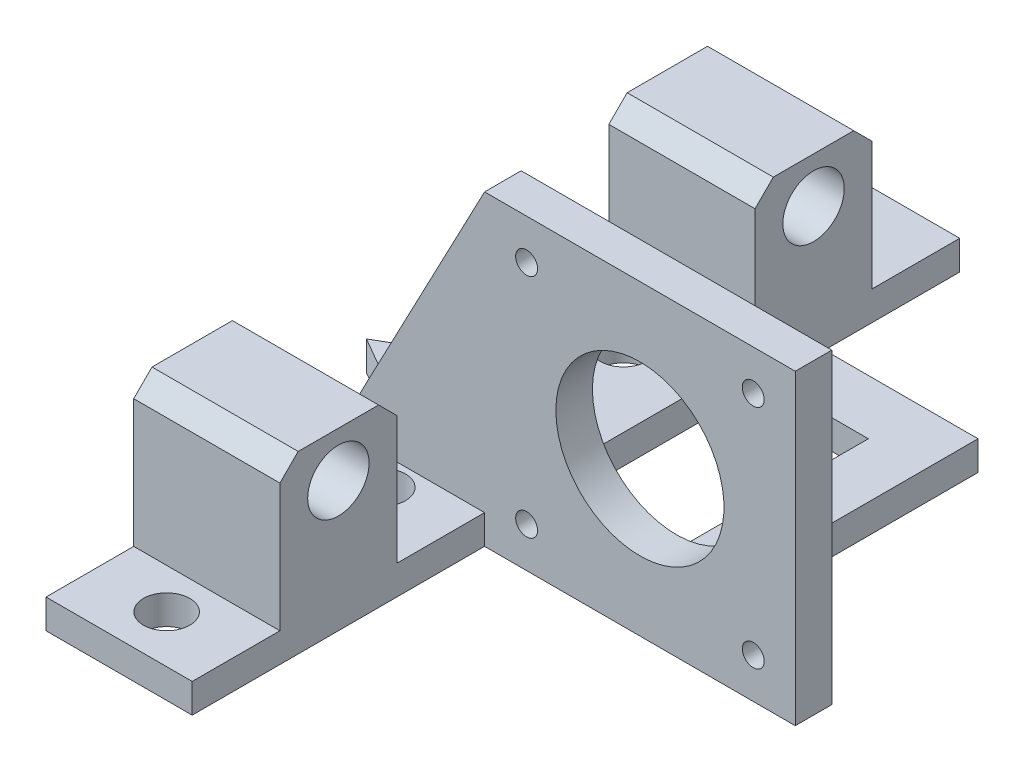
SolidWorks part; units mm, degrees
ref_plane "Front Plane" through (0, 0, 0) normal (0, 0, 1) x (1, 0, 0)
ref_plane "Top Plane" through (0, 0, 0) normal (0, 1, 0) x (1, 0, 0)
ref_plane "Right Plane" through (0, 0, 0) normal (1, 0, 0) x (0, 0, -1)
sketch "Sketch1" plane through (0, 0, 0) normal (0, 1, 0) x (1, 0, 0)
  line L1 (0, 0) -> (20, 0)
  line L2 (0, 0) -> (0, 105)
  line L3 (0, 105) -> (20, 105)
  line L4 (20, 0) -> (20, 105)
  dimension "D1" = 105
  dimension "D2" = 20
extrude "Boss-Extrude1" add sketch "Sketch1" along normal blind 4
sketch "Sketch2" plane through (0, 0, 0) normal (-1, 0, 0) x (0, 0, 1)
  line L0 (-105, 0) -> (0, 0) construction
  line L5 (-12, 21.5) -> (-14.5, 24)
  line L6 (-93, 0) -> (-77, 0)
  line L7 (-93, 0) -> (-93, 24)
  line L8 (-93, 24) -> (-77, 24)
  line L9 (-77, 0) -> (-77, 24)
  line L10 (-105, 0) -> (-93, 0) construction
  line L11 (-79.5, 24) -> (-77, 21.5)
  line L12 (-93, 21.5) -> (-90.5, 24)
  line L13 (-52.5, 0) -> (-52.5, 4) construction
  line L14 (-25.5, 24) -> (-28, 21.5)
  line L15 (-105, 4) -> (0, 4) construction
  line L16 (-28, 0) -> (-28, 24)
  line L17 (-12, 24) -> (-28, 24)
  line L18 (-12, 0) -> (-12, 24)
  line L19 (-12, 0) -> (-28, 0)
  circle A0 centre (-85, 17.8) radius 4.2
  circle A1 centre (-20, 17.8) radius 4.2
  point P10 (-85, 24)
  point P25 (-52.5, 4)
  point P30 (-20, 24)
  line M15 (0, 4) -> (-105, 4)
  dimension "D4" = 8.4
  dimension "D2" = 16
  dimension "D3" = 24
  dimension "D6" = 2.5
  dimension "D7" = 2.5
  dimension "D8" = 2.5
  dimension "D9" = 2.5
  dimension "D1" = 65
  dimension "D5" = 6.2
extrude "Boss-Extrude2" add sketch "Sketch2" against normal up to surface (20 mm away) contours L18 L5 L17 L14 L16 A1 M15 | L12 L7 L9 L11 L8 A0 M15 region at (0, 12.963, -20) region at (0, 12.963, -85) up to face at (20, 2, -52.5)
sketch "Sketch3" plane through (0, 0, 0) normal (0, -1, 0) x (1, 0, 0)
  line L0 (0, -57.5) -> (-8.6603, -52.5)
  line L1 (0, -105) -> (0, 0) construction
  line L2 (-8.6603, -52.5) -> (0, -47.5)
  line L3 (0, -57.5) -> (0, -47.5)
  point P6 (0, -52.5)
  dimension "D1" = 10
  dimension "D2" = 10
  dimension "D3" = 10
extrude "Boss-Extrude3" add sketch "Sketch3" against normal up to surface (4 mm away) up to face at (10, 4, -99)
sketch "Sketch4" plane through (0, 4, 0) normal (0, 1, 0) x (1, 0, 0)
  line L0 (10, 105) -> (10, 0) construction
  line L1 (20, 105) -> (0, 105) construction
  line L2 (0, 0) -> (20, 0) construction
  circle A0 centre (10, 98.5) radius 3.175
  circle A1 centre (10, 69) radius 3.175
  circle A2 centre (10, 36) radius 3.175
  circle A3 centre (10, 6.5) radius 3.175
  dimension "D1" = 6.35
  dimension "D2" = 6.5
  dimension "D3" = 36
  dimension "D4" = 6.5
  dimension "D5" = 36
extrude "Cut-Extrude1" cut sketch "Sketch4" against normal through all
sketch "Sketch5" plane through (20, 0, 0) normal (1, 0, 0) x (0, 0, -1)
  line L0 (0, 0) -> (105, 0) construction
  line L1 (45, 0) -> (40, 0)
  line L2 (45, 0) -> (45, 42)
  line L3 (45, 42) -> (40, 42)
  line L4 (40, 0) -> (40, 42)
  dimension "D1" = 42
  dimension "D2" = 5
  dimension "D3" = 7.5
extrude "Boss-Extrude4" add sketch "Sketch5" along normal blind 42.5
sketch "Sketch6" plane through (0, 0, -45) normal (0, 0, -1) x (-1, 0, 0)
  line L0 (-41.25, 42) -> (-41.25, 0) construction
  line L1 (-62.5, 42) -> (-20, 42) construction
  line L2 (-62.5, 0) -> (-20, 0) construction
  line L3 (-62.5, 21) -> (-20, 21) construction
  line L4 (-62.5, 0) -> (-62.5, 42) construction
  line L5 (-20, 4) -> (-20, 42) construction
  circle A0 centre (-41.25, 21) radius 11.5
  circle A1 centre (-56.75, 36.5) radius 1.5
  circle A5 centre (-25.75, 36.5) radius 1.5
  circle A6 centre (-25.75, 5.5) radius 1.5
  circle A7 centre (-56.75, 5.5) radius 1.5
  dimension "D3" = 3
  dimension "D4" = 23
  dimension "D1" = 15.5
  dimension "D2" = 15.5
extrude "Cut-Extrude2" cut sketch "Sketch6" against normal through all
sketch "Sketch7" plane through (0, 0, -40) normal (0, 0, 1) x (1, 0, 0)
  line L0 (20, 42) -> (0, 4)
  line L1 (0, 4) -> (20, 4)
  line L2 (20, 4) -> (20, 42)
extrude "Boss-Extrude5" add sketch "Sketch7" against normal up to surface (5 mm away) up to face at (58.25, 5.5, -45)
sketch "Sketch8" plane through (0, 0, 0) normal (0, -1, 0) x (1, 0, 0)
  line L0 (45, -45) -> (45, -82.5)
  line L1 (62.5, -45) -> (20, -45) construction
  line L2 (45, -82.5) -> (20, -82.5)
  line L3 (20, -45) -> (20, -105) construction
  line L4 (20, -82.5) -> (20, -75)
  line L5 (20, -75) -> (37.5, -75)
  line L6 (37.5, -75) -> (37.5, -45)
  line L7 (37.5, -45) -> (45, -45)
  point P11 (41.25, -45)
  point P12 (41.25, -45)
  dimension "D1" = 7.5
extrude "Boss-Extrude6" add sketch "Sketch8" against normal up to surface (4 mm away) up to face at (10, 4, -3.325)
equation "\"8mm hole\" = 8.4mm"
equation "\"D4@Sketch2\"= \"8mm hole\""
equation "\"22mm hole\"= 23mm"
equation "\"15mm hole\"= 15.8mm"
equation "\"bed height offset\"= 3mm"
equation "\"D3@Sketch2\"= 21 + \"bed height offset\""
equation "\"D4@Sketch6\"= \"22mm hole\""
